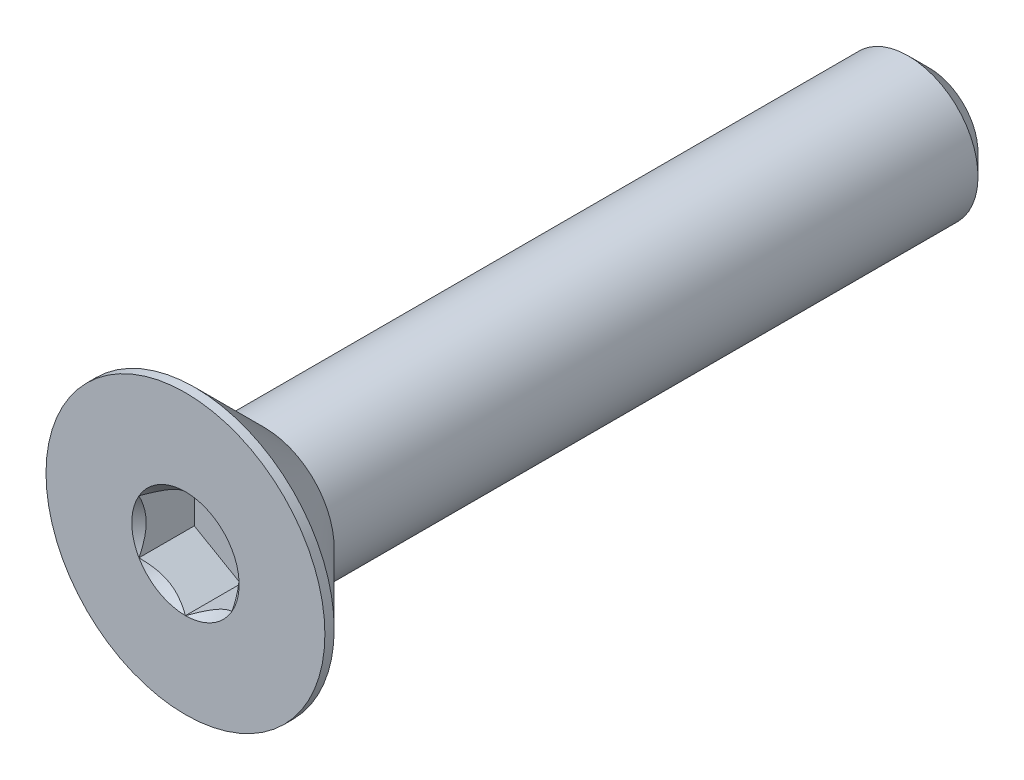
SolidWorks part; units mm, degrees
material "Alloy Steel"
ref_plane "Front" through (0, 0, 0) normal (0, 0, 1) x (1, 0, 0)
ref_plane "Top" through (0, 0, 0) normal (0, 1, 0) x (1, 0, 0)
ref_plane "Right" through (0, 0, 0) normal (1, 0, 0) x (0, 0, -1)
sketch "Sketch1" plane through (0, 0, 0) normal (1, 0, 0) x (0, 0, -1)
  line L0 (-8, 3) -> (-7.8, 3) construction
  line L1 (-7.8, 3) -> (-6.3, 1.5) construction
  line L2 (-8, 1.5) -> (8, 1.5) construction
  line L3 (8, 1.5) -> (8, 0) construction
  line L4 (8, 0) -> (-8, 0) construction
  line L5 (-8, 0) -> (-8, 3) construction
  line L6 (-8, 3) -> (-8, -3) construction
  line L7 (8, 1.5) -> (8, -1.5) construction
  line L8 (-8, -3) -> (-7.8, -3) construction
  line L9 (-7.8, -3) -> (-6.3, -1.5) construction
  line L11 (-8, 1.5) -> (-8, 0) construction
  line L12 (-6.3, 1.5) -> (-6.3, 0) construction
  line L13 (7.9688, 1.5541) -> (8.2188, 1.1211) construction
  line L14 (8.2188, 1.1211) -> (8.4687, 1.5541) construction
  line L15 (8.4687, 1.5541) -> (7.9688, 1.5541) construction
  line L16 (8.2188, 1.5541) -> (8.2188, 1.5) construction
  line L17 (8.2188, 1.5) -> (8.2188, 1.1752) construction
  line L18 (8.2188, 1.1752) -> (8.2188, 1.1211) construction
  line L19 (8.2188, 1.5271) -> (8.4531, 1.5271) construction
  line L20 (8.2188, 1.5271) -> (7.9844, 1.5271) construction
  line L21 (8, 1.5) -> (8.4375, 1.5) construction
  line L22 (8.1875, 1.1752) -> (8.25, 1.1752) construction
  line L23 (8, -1.5) -> (-6.3, -1.5) construction
  point P10 (6.75, -1.5)
  point P24 (-6.3, 1.5)
  point P30 (0, 0)
  dimension "Head Diameter" = 6
  dimension "Head Height" = 1.7
  dimension "Length" = 16
  dimension "Countersink Angle" = 90
  dimension "Thread Pitch" = 0.5
  dimension "D2" = 0.0625
  dimension "Minimum Thread Length" = 14.3
  dimension "Thread Size" = 3
  dimension "D1" = 1.25
sketch "Sketch2" plane through (0, 0, 0) normal (0, 0, 1) x (1, 0, 0)
  line L1 (0, 1.1547) -> (-1, 0.5774) construction
  line L2 (-1, 0.5774) -> (-1, -0.5774) construction
  line L3 (-1, -0.5774) -> (0, -1.1547) construction
  line L4 (0, -1.1547) -> (1, -0.5774) construction
  line L5 (1, -0.5774) -> (1, 0.5774) construction
  line L6 (1, 0.5774) -> (0, 1.1547) construction
  circle A0 centre (0, 0) radius 1 construction
  dimension "Drive Size" = 2
sketch "Sketch3" plane through (0, 0, 0) normal (1, 0, 0) x (0, 0, -1)
  line L0 (-8, 1.5) -> (8, 1.5)
  line L1 (8, 1.5) -> (8, 0)
  line L2 (8, 0) -> (-8, 0)
  line L3 (-8, 0) -> (-8, 1.5)
revolve "Revolve1" add sketch "Sketch3" angle 360 about L4
chamfer "Chamfer1" distance 0.45 angle 45 1 edges at (0, 1.5, -8)
sketch "Sketch6" plane through (0, 0, 0) normal (1, 0, 0) x (0, 0, -1)
  line L0 (-8, 3) -> (-7.8, 3)
  line L1 (-7.8, 3) -> (-6.3, 1.5)
  line L2 (-6.3, 1.5) -> (-6.3, 0)
  line L3 (-6.3, 0) -> (-8, 0)
  line L4 (-8, 0) -> (-8, 3)
revolve "Revolve2" add sketch "Sketch6" angle 360 about L4
sketch "Sketch8" plane through (0, 0, 8) normal (0, 0, 1) x (1, 0, 0)
  line L0 (0, 1.1547) -> (-1, 0.5774) construction
  line L1 (1, 0.5774) -> (0, 1.1547) construction
  line L2 (1, -0.5774) -> (1, 0.5774) construction
  line L3 (0, -1.1547) -> (1, -0.5774) construction
  line L4 (-1, 0.5774) -> (-1, -0.5774) construction
  line L5 (-1, -0.5774) -> (0, -1.1547) construction
  line L6 (0, 1.1547) -> (-1, 0.5774)
  line L7 (1, 0.5774) -> (0, 1.1547)
  line L8 (1, -0.5774) -> (1, 0.5774)
  line L9 (0, -1.1547) -> (1, -0.5774)
  line L10 (-1, 0.5774) -> (-1, -0.5774)
  line L11 (-1, -0.5774) -> (0, -1.1547)
extrude "Cut-Extrude1" cut sketch "Sketch8" against normal blind 1.19
sketch "Sketch9" plane through (0, 0, 8) normal (0, 0, 1) x (1, 0, 0)
  circle A0 centre (0, 0) radius 1.1547
extrude "Cut-Extrude2" cut sketch "Sketch9" against normal up to next (1.19 mm away) draft 45
ref_plane "Plane1" [suppressed] through (0, 0, 6.3) normal (0, 0, 1) x (1, 0, 0)
split "Split1" [suppressed] bodies to split 124
sketch "Sketch4" [suppressed] plane through (0, 0, -8) normal (0, 0, -1) x (-1, 0, 0)
  circle A0 centre (0, 0) radius 1.5 construction
  circle A1 centre (0, 0) radius 1.5
curve "Helix/Spiral1" [suppressed] pitch 0.5 height 14.8 turns 29.6
sketch "Sketch10" [suppressed] plane through (0, 0, 0) normal (1, 0, 0) x (0, 0, -1)
  line L0 (7.9844, 1.5271) -> (8.4531, 1.5271)
  line L1 (8.4531, 1.5271) -> (8.25, 1.1752)
  line L2 (8.25, 1.1752) -> (8.1875, 1.1752)
  line L3 (8.1875, 1.1752) -> (7.9844, 1.5271)
sweep "Cut-Sweep1" [suppressed] cut profiles "Sketch10" path "Helix/Spiral1"
equation "\"D2@Sketch1\" = \"Thread Pitch@Sketch1\" / 8"
equation "\"D4@Helix/Spiral1\"=\"Thread Pitch@Sketch1\""
equation "\"D3@Helix/Spiral1\"=\"Minimum Thread Length@Sketch1\"+\"Thread Pitch@Sketch1\""
equation "\"D1@Chamfer1\"=\"Thread Size@Sketch1\"*.15"
equation "\"D1@Cut-Extrude1\"=\"Head Height@Sketch1\"*.7"
equation "\"D1@Sketch1\"=\"Thread Pitch@Sketch1\"*2.5"
